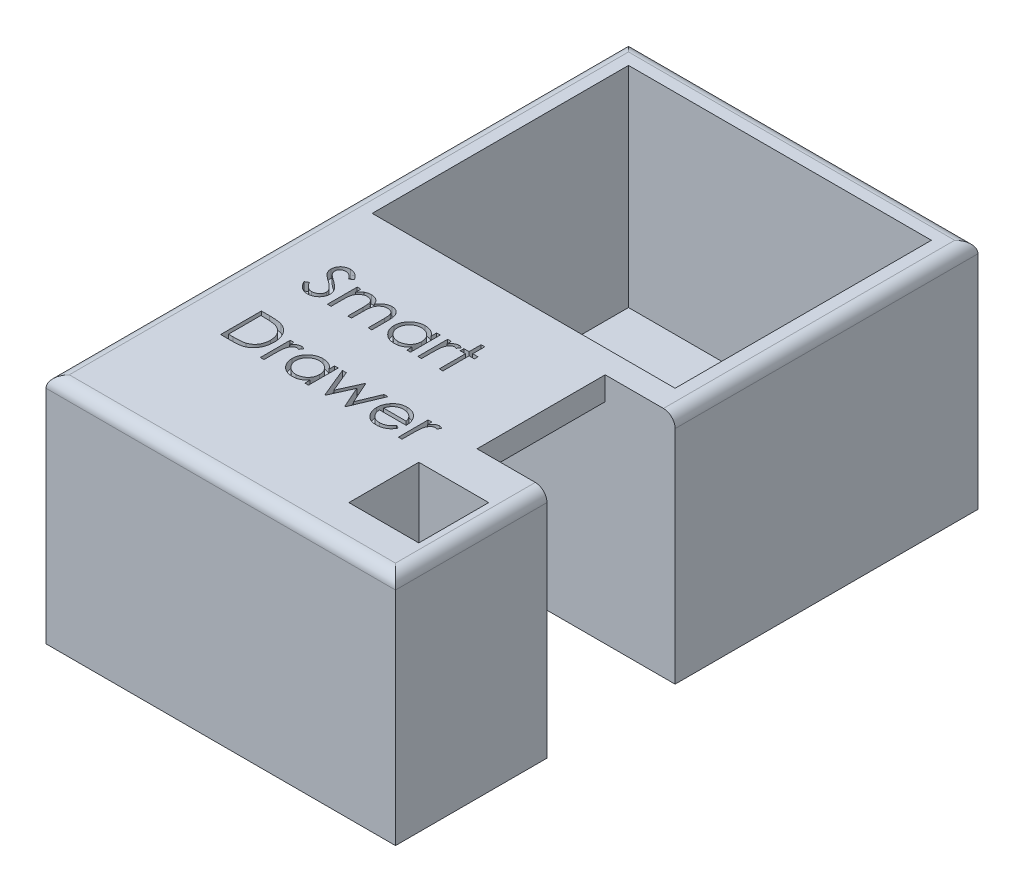
SolidWorks part; units mm, degrees
ref_plane "Front Plane" through (0, 0, 0) normal (0, 0, 1) x (1, 0, 0)
ref_plane "Top Plane" through (0, 0, 0) normal (0, 1, 0) x (1, 0, 0)
ref_plane "Right Plane" through (0, 0, 0) normal (1, 0, 0) x (0, 0, -1)
sketch "Sketch1" plane through (0, 0, 0) normal (0, 1, 0) x (1, 0, 0)
  line L0 (15, 25) -> (15, -1)
  line L1 (-15, 25) -> (15, 25)
  line L2 (-15, 25) -> (-15, -25)
  line L3 (-15, -25) -> (15, -25)
  line L4 (15, -12) -> (15, -25)
  line L5 (-15, 25) -> (15, -25) construction
  line L6 (-15, -25) -> (15, 25) construction
  line L7 (15, -12) -> (-12, -12)
  line L9 (15, -1) -> (-12, -1)
  line L10 (-12, -12) -> (-12, -1)
  point P0 (0, 0)
  dimension "D1" = 50
  dimension "D2" = 30
  dimension "D3" = 13
  dimension "D4" = 11
  dimension "D5" = 3
extrude "Boss-Extrude1" add sketch "Sketch1" along normal blind 2
sketch "Sketch2" plane through (0, 2, 0) normal (0, 1, 0) x (1, 0, 0)
  line L1 (-13, 23) -> (13, 23)
  line L2 (-15, 25) -> (-15, -25)
  line L3 (13, 23) -> (13, 1)
  line L4 (15, -25) -> (-15, -25)
  line L5 (13, 1) -> (-13, 1)
  line L6 (-13, 23) -> (-13, 1)
  line L7 (-15, 25) -> (15, 25)
  line L8 (15, 25) -> (15, -1)
  line L9 (15, -1) -> (-12, -1)
  line L11 (7.5, -15.5) -> (13.5, -15.5)
  line L12 (7.5, -15.5) -> (7.5, -21.5)
  line L13 (7.5, -21.5) -> (13.5, -21.5)
  line L14 (15, -12) -> (15, -25)
  line L15 (-12, -1) -> (-12, -12)
  line L16 (-12, -12) -> (15, -12)
  line L17 (15, -12) -> (14.9214, -12.3163)
  line L18 (13.5, -15.5) -> (13.5, -21.5)
  line L19 (7.5, -15.5) -> (13.5, -21.5) construction
  line L20 (7.5, -21.5) -> (13.5, -15.5) construction
  point P1 (10.5, -18.5)
  line M10 (15, -25) -> (15, -12)
  line M11 (15, -12) -> (-12, -12)
  line M13 (-12, -1) -> (15, -1)
  line M14 (15, -1) -> (15, 25)
  line M15 (15, 25) -> (-15, 25)
  line M16 (-15, 25) -> (-15, -25)
  line M17 (-15, -25) -> (15, -25)
  dimension "D1" = 2
  dimension "D2" = 2
  dimension "D3" = 2
  dimension "D4" = 2
  dimension "D5" = 6.5
  dimension "D6" = 4.5
  dimension "D7" = 6
  dimension "D8" = 6
extrude "Boss-Extrude3" add sketch "Sketch2" along normal blind 18 contours L6 M13 M14 M15 M16 M17 M10 M11 region at (0, 2, -24.4169)
sketch "Sketch3" plane through (0, 2, 0) normal (0, 1, 0) x (1, 0, 0)
  line L2 (15, 25) -> (-15, 25) construction
  line L3 (15, -1) -> (15, 25) construction
  line L5 (15, -25) -> (15, -12) construction
  line L6 (15, -12) -> (-12, -12) construction
  circle A0 centre (10.5, 20.5) radius 1.25
  circle A1 centre (10.5, -18.5) radius 1.25
  dimension "D1" = 2.5
  dimension "D3" = 6.5
  dimension "D4" = 2.5
  dimension "D2" = 4.5
  dimension "D5" = 4.5
  dimension "D6" = 4.5
extrude "Cut-Extrude1" cut sketch "Sketch3" against normal through all
fillet "Fillet1" radius 1 5 edges at (15, 20, -12) (0, 20, -25) (-15, 20, 0) (15, 20, 18.5) (0, 20, 25)
sketch "Sketch4" plane through (0, 0, 1) normal (0, 0, 1) x (1, 0, 0)
  line L0 (15, 19) -> (15, 0) construction
  line L1 (-12, 20) -> (9, 20)
  line L2 (-12, 20) -> (-12, 18)
  line L3 (-12, 18) -> (9, 18)
  line L4 (9, 20) -> (9, 18)
  dimension "D1" = 2
  dimension "D2" = 6
extrude "Boss-Extrude4" add sketch "Sketch4" along normal up to surface (11 mm away) up to face at (4.0414, 11.8414, 12)
sketch "Sketch5" plane through (0, 20, 0) normal (0, 1, 0) x (1, 0, 0)
  text T0 "Smart \r\nDrawer"
extrude "Cut-Extrude2" cut sketch "Sketch5" against normal blind 0.7
